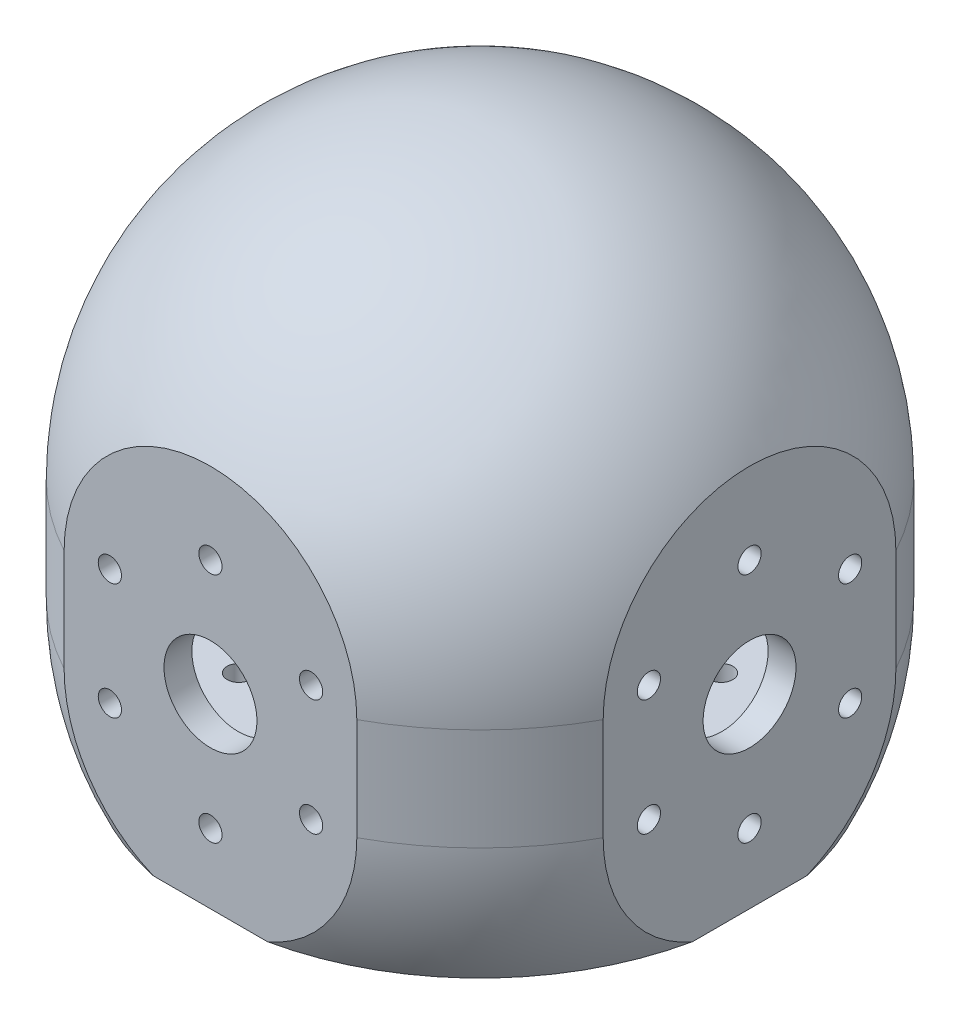
SolidWorks part; units mm, degrees
ref_plane "Front Plane" through (0, 0, 0) normal (0, 0, 1) x (1, 0, 0)
ref_plane "Top Plane" through (0, 0, 0) normal (0, 1, 0) x (1, 0, 0)
ref_plane "Right Plane" through (0, 0, 0) normal (1, 0, 0) x (0, 0, -1)
sketch "Main Revolve Sketch" plane through (0, 0, 0) normal (0, 0, 1) x (1, 0, 0)
  line L0 (0, 0) -> (0, 96.25)
  line L3 (-82.5, 13.75) -> (-82.5, 0)
  line L4 (-82.5, 0) -> (-82.5, -13.75)
  line L8 (0, 96.25) -> (96.25, 96.25) construction
  line L9 (0, -96.25) -> (96.25, -96.25) construction
  line L10 (-74.1093, -50) -> (0, -50)
  line L11 (0, 0) -> (0, -96.25) construction
  line L13 (0, 0) -> (0, -50)
  arc A0 (0, 96.25) -> (-82.5, 13.75) centre (0, 13.75) ccw
  arc A1 (-82.5, -13.75) -> (-74.1093, -50) centre (0, -13.75) ccw
  dimension "D1" = 82.5
  dimension "D2" = 27.5
  dimension "D3" = 50
revolve "Main Revolve" add sketch "Main Revolve Sketch" angle 360 about L0
sketch "Sketch3" plane through (0, 0, 0) normal (0, 0, 1) x (1, 0, 0)
  line L0 (0, 0) -> (-27.0633, -15.625) construction
  line L1 (-27.0633, -15.625) -> (-27.0633, 15.625) construction
  line L2 (-27.0633, 15.625) -> (0, 0) construction
  line L3 (0, 0) -> (0, 31.25) construction
  line L4 (0, 31.25) -> (27.0633, 15.625) construction
  line L5 (27.0633, 15.625) -> (0, 0) construction
  line L6 (0, 0) -> (27.0633, -15.625) construction
  line L7 (0, -31.25) -> (27.0633, -15.625) construction
  line L11 (0, -31.25) -> (0, 0) construction
  line L12 (-27.0633, 15.625) -> (0, 31.25) construction
  line L13 (27.0633, 15.625) -> (27.0633, -15.625) construction
  line L14 (-27.0633, -15.625) -> (0, -31.25) construction
  circle A0 centre (0, 0) radius 12.5
  circle A1 centre (0, 31.25) radius 3.125
  circle A2 centre (27.0633, 15.625) radius 3.125
  circle A3 centre (27.0633, -15.625) radius 3.125
  circle A6 centre (0, -31.25) radius 3.125
  circle A7 centre (-27.0633, -15.625) radius 3.125
  circle A8 centre (-27.0633, 15.625) radius 3.125
  circle A9 centre (0, 0) radius 96.25
  arc A10 (82.5, 13.75) -> (-82.5, 13.75) centre (0, 13.75) ccw construction
  dimension "D1" = 25
  dimension "D3" = 6.25
  dimension "D2" = 31.25
extrude "Cut-Extrude2" cut sketch "Sketch3" against normal offset from surface (427.5 mm away) 72.5 from offset 500 contours A9 up to plane "Front Plane"
pattern_circular "CirPattern4" count 4 over 360 about axis through (0, 0, 0) along (0, -1, 0) of "Cut-Extrude2"
shell "Shell2" thickness 7.5 removed face at (0, -50, 0)
extrude "Cut-Extrude3" cut sketch "Sketch3<3>" against normal through all contours A3 | A2 | A1 | A0 | A8 | A7 | A6
sketch "Sketch3<3>" plane through (0, 0, 0) normal (0, 0, 1) x (1, 0, 0) same geometry as "Sketch3"
pattern_circular "CirPattern5" count 4 over 360 about axis through (0, 0, 0) along (0, -1, 0) of "Cut-Extrude3" reverse direction yes
sketch "Sketch5" plane through (0, 0, 0) normal (0, 1, 0) x (1, 0, 0)
  line L0 (-72.5, 15.3603) -> (-72.5, -15.3603) construction
  line L1 (15.3603, 72.5) -> (-15.3603, 72.5) construction
  line L2 (72.5, -15.3603) -> (72.5, 15.3603) construction
  line L3 (-15.3603, -72.5) -> (15.3603, -72.5) construction
  line L4 (-72.5, 15.3603) -> (-72.5, -15.3603)
  line L5 (15.3603, 72.5) -> (-15.3603, 72.5)
  line L6 (72.5, -15.3603) -> (72.5, 15.3603)
  line L7 (-15.3603, -72.5) -> (15.3603, -72.5)
  line L8 (0, 0) -> (0, -47.5) construction
  line L9 (-23.75, 41.1362) -> (0, 47.5) construction
  line L10 (47.5, 0) -> (0, 0) construction
  line L11 (0, 0) -> (41.1362, 23.75) construction
  line L12 (41.1362, 23.75) -> (23.75, 41.1362) construction
  line L13 (23.75, 41.1362) -> (0, 0) construction
  line L14 (0, 0) -> (0, 47.5) construction
  line L15 (0, 47.5) -> (23.75, 41.1362) construction
  line L16 (-23.75, 41.1362) -> (0, 0) construction
  line L17 (0, 0) -> (-41.1362, 23.75) construction
  line L18 (-41.1362, 23.75) -> (-47.5, 0) construction
  line L19 (-47.5, 0) -> (0, 0) construction
  line L20 (0, 0) -> (-41.1362, -23.75) construction
  line L21 (47.5, 0) -> (41.1362, 23.75) construction
  line L22 (-23.75, 41.1362) -> (-41.1362, 23.75) construction
  line L23 (-41.1362, -23.75) -> (-47.5, 0) construction
  line L24 (0, 0) -> (-23.75, -41.1362) construction
  line L25 (0, 0) -> (41.1362, -23.75) construction
  line L26 (-23.75, -41.1362) -> (-41.1362, -23.75) construction
  line L29 (41.1362, -23.75) -> (47.5, 0) construction
  line L30 (-23.75, -41.1362) -> (0, -47.5) construction
  line L31 (0, -47.5) -> (23.75, -41.1362) construction
  line L32 (23.75, -41.1362) -> (41.1362, -23.75) construction
  line L33 (0, 0) -> (23.75, -41.1362) construction
  arc A0 (-15.3603, 72.5) -> (-72.5, 15.3603) centre (0, 0) ccw construction
  arc A1 (72.5, 15.3603) -> (15.3603, 72.5) centre (0, 0) ccw construction
  arc A2 (15.3603, -72.5) -> (72.5, -15.3603) centre (0, 0) ccw construction
  arc A3 (-72.5, -15.3603) -> (-15.3603, -72.5) centre (0, 0) ccw construction
  arc A4 (-15.3603, 72.5) -> (-72.5, 15.3603) centre (0, 0) ccw
  arc A5 (72.5, 15.3603) -> (15.3603, 72.5) centre (0, 0) ccw
  arc A6 (15.3603, -72.5) -> (72.5, -15.3603) centre (0, 0) ccw
  arc A7 (-72.5, -15.3603) -> (-15.3603, -72.5) centre (0, 0) ccw
  circle A8 centre (0, 0) radius 40
  circle A9 centre (0, -47.5) radius 3.125
  circle A10 centre (47.5, 0) radius 3.125
  circle A11 centre (41.1362, 23.75) radius 3.125
  circle A12 centre (23.75, 41.1362) radius 3.125
  circle A13 centre (0, 47.5) radius 3.125
  circle A14 centre (-23.75, 41.1362) radius 3.125
  circle A15 centre (-41.1362, 23.75) radius 3.125
  circle A16 centre (-47.5, 0) radius 3.125
  circle A17 centre (-41.1362, -23.75) radius 3.125
  circle A18 centre (41.1362, -23.75) radius 3.125
  circle A19 centre (-23.75, -41.1362) radius 3.125
  circle A20 centre (23.75, -41.1362) radius 3.125
  dimension "D1" = 80
  dimension "D3" = 6.25
  dimension "D2" = 47.5
extrude "Boss-Extrude1" add sketch "Sketch5" along normal blind 10 from surface starting at face at (0, -50, 0)
